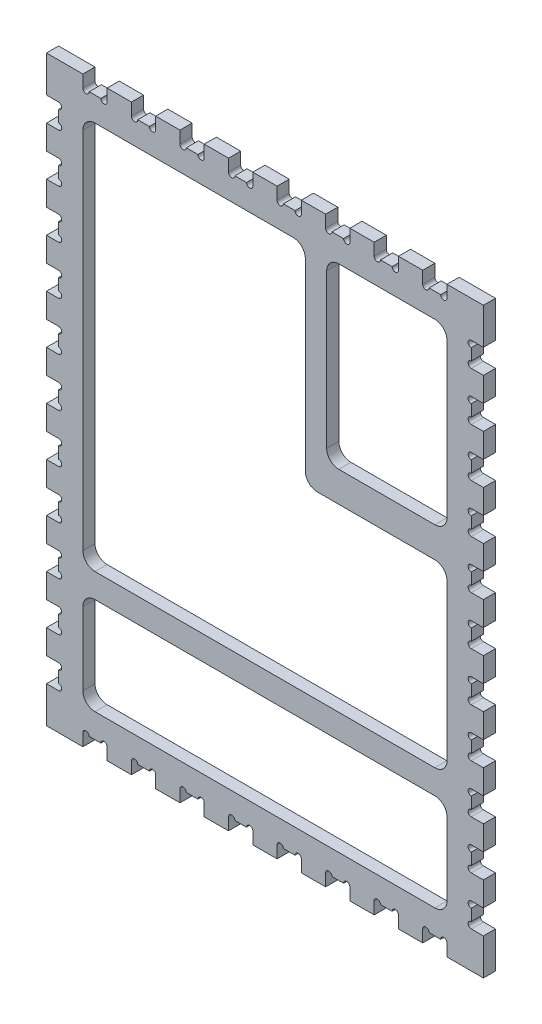
SolidWorks part; units mm, degrees
ref_plane "Front Plane" through (0, 0, 0) normal (0, 0, 1) x (1, 0, 0)
ref_plane "Top Plane" through (0, 0, 0) normal (0, 1, 0) x (1, 0, 0)
ref_plane "Right Plane" through (0, 0, 0) normal (1, 0, 0) x (0, 0, -1)
sketch "Sketch1" plane through (0, 0, 0) normal (0, 0, 1) x (1, 0, 0)
  line L1 (228.6, -304.8) -> (-228.6, -304.8)
  line L2 (228.6, -304.8) -> (228.6, 304.8)
  line L3 (228.6, 304.8) -> (-228.6, 304.8)
  line L4 (-228.6, -304.8) -> (-228.6, 304.8)
  line L5 (228.6, -304.8) -> (-228.6, 304.8) construction
  line L6 (228.6, 304.8) -> (-228.6, -304.8) construction
  line L9 (-203.2, 304.8) -> (-228.6, 304.8) construction
  point P0 (0, 0)
  dimension "D1" = 457.2
  dimension "D2" = 609.6
extrude "Boss-Extrude1" add sketch "Sketch1" along normal blind 12.7
sketch "Sketch2" plane through (0, 0, 12.7) normal (0, 0, 1) x (1, 0, 0)
  line L0 (228.6, 304.8) -> (-228.6, 304.8) construction
  line L1 (-190.5, 292.1) -> (-228.6, 292.1) construction
  line L2 (-190.5, 304.8) -> (-165.1, 304.8)
  line L3 (-190.5, 304.8) -> (-190.5, 292.1)
  line L4 (-190.5, 292.1) -> (-165.1, 292.1)
  line L5 (-165.1, 304.8) -> (-165.1, 292.1)
  line L6 (-228.6, 304.8) -> (-228.6, -304.8) construction
  circle A0 centre (-187.198, 292.1) radius 3.302
  circle A1 centre (-168.402, 292.1) radius 3.302
  line M10 (228.6, 304.8) -> (-228.6, 304.8)
  dimension "D4" = 6.604
  dimension "D5" = 6.604
  dimension "D1" = 25.4
  dimension "D2" = 12.7
  dimension "D3" = 38.1
extrude "Cut-Extrude1" cut sketch "Sketch2" against normal through all contours A1 L5 L3 A0 L4 M10 | L4 A0 | L4 A0 | L4 A1 | L4 A1 region at (-177.8, 299.0379, 12.7) region at (-187.198, 293.5014, 12.7) region at (-187.198, 290.6986, 12.7) region at (-168.402, 290.6986, 12.7) region at (-168.402, 293.5014, 12.7)
pattern_linear "LPattern1" count 8 spacing 50.8 along (1, 0, 0) of "Cut-Extrude1"
sketch "Sketch3" plane through (0, 0, 12.7) normal (0, 0, 1) x (1, 0, 0)
  line L0 (-228.6, 304.8) -> (-228.6, -304.8) construction
  line L1 (-228.6, 266.7) -> (-215.9, 266.7)
  line L2 (-228.6, 266.7) -> (-228.6, 241.3)
  line L3 (-228.6, 241.3) -> (-215.9, 241.3)
  line L4 (-215.9, 266.7) -> (-215.9, 241.3)
  line L5 (-215.9, 266.7) -> (-215.9, 304.8) construction
  line L7 (-190.5, 304.8) -> (-228.6, 304.8) construction
  circle A0 centre (-215.9, 263.398) radius 3.302
  circle A1 centre (-215.9, 244.602) radius 3.302
  dimension "D3" = 6.604
  dimension "D4" = 6.604
  dimension "D1" = 25.4
  dimension "D2" = 12.7
  dimension "D5" = 38.1
extrude "Cut-Extrude2" cut sketch "Sketch3" against normal through all contours A1 L4 A0 L1 L2 L3 | L4 A0 | L4 A1 | L4 A1 | L4 A0 region at (-222.8379, 254, 12.7) region at (-214.4986, 263.398, 12.7) region at (-217.3014, 263.398, 12.7) region at (-217.3014, 244.602, 12.7) region at (-214.4986, 244.602, 12.7)
pattern_linear "LPattern2" count 11 spacing 50.8 along (0, -1, 0) of "Cut-Extrude2"
ref_plane "Plane1" through (0, 0, 0) normal (1, 0, 0) x (0, 0, -1)
ref_plane "Plane2" through (0, 0, 0) normal (0, 1, 0) x (1, 0, 0)
mirror "Mirror1" about plane through (0, 0, 0) normal (1, 0, 0) of "LPattern2"
mirror "Mirror2" about plane through (0, 0, 0) normal (0, 1, 0) of "LPattern1"
sketch "Sketch4" plane through (0, 0, 0) normal (0, 0, -1) x (-1, 0, 0)
  line L0 (-193.5982, 285.75) -> (-193.5982, 61.468) construction
  line L9 (190.5, -266.7) -> (-190.5, -266.7)
  line L10 (190.5, -266.7) -> (190.5, -165.1)
  line L11 (190.5, -165.1) -> (-190.5, -165.1)
  line L12 (-190.5, -266.7) -> (-190.5, -165.1)
  line L13 (-193.5982, 61.468) -> (-61.5182, 61.468) construction
  line L14 (-61.5182, 61.468) -> (-61.5182, 285.75) construction
  line L15 (-61.5182, 285.75) -> (-193.5982, 285.75) construction
  line L16 (0, -266.7) -> (0, -304.8) construction
  line L17 (12.7, -304.8) -> (-12.7, -304.8) construction
  line L18 (-127.5582, 61.468) -> (-127.5582, 86.868) construction
  line L19 (-64.6164, 266.7) -> (-42.2644, 266.7) construction
  line L20 (-190.5, -139.7) -> (190.5, -139.7)
  line L21 (190.5, -139.7) -> (190.5, 266.7)
  line L22 (190.5, 266.7) -> (-42.2644, 266.7)
  line L23 (-42.2644, 266.7) -> (-42.2644, 48.768)
  line L24 (-42.2644, 48.768) -> (-190.5, 48.768)
  line L25 (-190.5, 48.768) -> (-190.5, -139.7)
  line L26 (190.5, -266.7) -> (215.9, -266.7) construction
  line L27 (-187.452, 260.35) -> (-67.6644, 86.868) construction
  line L28 (-187.452, 260.35) -> (-67.6644, 260.35) construction
  line L29 (-187.452, 260.35) -> (-187.452, 86.868) construction
  line L30 (-187.452, 86.868) -> (-67.6644, 86.868) construction
  line L31 (-67.6644, 260.35) -> (-67.6644, 86.868) construction
  line L32 (-190.5, 80.518) -> (-190.5, 48.768)
  line L33 (190.5, 292.1) -> (190.5, 266.7)
  line L34 (215.9, 266.7) -> (190.5, 266.7) construction
  line L36 (-190.5, 266.7) -> (-64.6164, 266.7)
  line L37 (-190.5, -139.7) -> (-190.5, -165.1) construction
  line L38 (190.5, -139.7) -> (190.5, -165.1) construction
  line L39 (-190.5, 266.7) -> (-190.5, 80.518)
  line L40 (-190.5, 80.518) -> (-64.6164, 80.518)
  line L41 (-64.6164, 266.7) -> (-64.6164, 80.518)
  dimension "D1" = 25.4
  dimension "D2" = 210.82
  dimension "D3" = 101.6
  dimension "D4" = 25.4
  dimension "D5" = 38.1
  dimension "D6" = 224.282
  dimension "D7" = 132.08
  dimension "D8" = 25.4
  dimension "D9" = 6.35
  dimension "D10" = 3.048
  dimension "D11" = 3.048
  dimension "D12" = 6.35
  dimension "D13" = 25.4
extrude "Cut-Extrude3" cut sketch "Sketch4" against normal through all contours L31 L28 L29 L30 | L24 L25 L20 L21 L22 L23 | L12 L9 L10 L11 | L39 L36 L41 L40 region at (0, -215.9, 0) region at (-30.6836, 38.6556, 0)
fillet "Fillet1" radius 12.7 14 edges at (190.5, -266.7, 6.35) (190.5, -139.7, 6.35) (-190.5, -165.1, 6.35) (-190.5, 266.7, 6.35) (-190.5, -266.7, 6.35) (-190.5, -139.7, 6.35) (190.5, 48.768, 6.35) (42.2644, 266.7, 6.35) (42.2644, 48.768, 6.35) (190.5, -165.1, 6.35) (64.6164, 266.7, 6.35) (64.6164, 80.518, 6.35) (190.5, 80.518, 6.35) (190.5, 266.7, 6.35)
